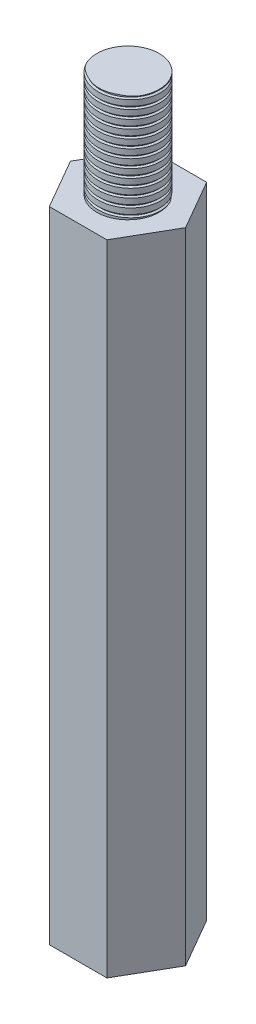
SolidWorks part; units mm, degrees
note: The reader was unsure of these and kept them because the rebuilt part matched: shared geometry of "草图1<3>".
ref_plane "前视基准面" through (0, 0, 0) normal (0, 0, 1) x (1, 0, 0)
ref_plane "上视基准面" through (0, 0, 0) normal (0, 1, 0) x (1, 0, 0)
ref_plane "右视基准面" through (0, 0, 0) normal (1, 0, 0) x (0, 0, -1)
sketch "草图1" plane through (0, 0, 0) normal (0, 1, 0) x (1, 0, 0)
  line L0 (0, 0) -> (0, 4.5761) construction
  line L1 (1.351, -2.34) -> (2.702, 0)
  line L2 (2.702, 0) -> (1.351, 2.34)
  line L3 (1.351, 2.34) -> (-1.351, 2.34)
  line L4 (-1.351, 2.34) -> (-2.702, 0)
  line L5 (-2.702, 0) -> (-1.351, -2.34)
  line L6 (-1.351, -2.34) -> (1.351, -2.34)
  line L7 (0, 4.5761) -> (0, -3.6794) construction
  circle A0 centre (0, 0) radius 2.34 construction
  circle A1 centre (0, 0) radius 1.46
  dimension "D1" = 4.68
  dimension "D2" = 2.92
extrude "凸台-拉伸1" add sketch "草图1" along normal blind 30 contours A1 | L5 L6 L1 L2 L3 L4 A1
extrude "切除-拉伸1" cut sketch "草图1<3>" along normal blind 5 contours A1
sketch "草图1<3>" plane through (0, 0, 0) normal (0, 1, 0) x (1, 0, 0) same geometry as "草图1"
sketch "草图2" plane through (0, 30, 0) normal (0, 1, 0) x (1, 0, 0)
  circle A0 centre (0, 0) radius 1.46
  dimension "D1" = 2.92
extrude "凸台-拉伸2" add sketch "草图2" along normal blind 5 separate body
ref_plane "基准面1" through (0, 0, 0) normal (0, 0, -1) x (-1, 0, 0)
sketch "草图4" plane through (0, 0, 0) normal (0, 0, -1) x (-1, 0, 0)
  line L0 (0, 0) -> (0, 28.5702) construction
  line L1 (-1.56, 30) -> (-1.56, 30.2)
  line L2 (-1.56, 30.2) -> (-1.36, 30.1333)
  line L3 (-1.36, 30.0667) -> (-1.56, 30)
  line L4 (-1.26, 30.1) -> (-2.0659, 30.1) construction
  line L5 (-2.0659, 30.1) -> (-0.8933, 30.1) construction
  line L7 (-1.46, 35) -> (-1.46, 30) construction
  line L8 (-1.36, 30.1333) -> (-1.36, 30.0667)
  line L9 (-1.46, 30) -> (1.46, 30) construction
  dimension "D1" = 0.1
  dimension "D2" = 0.1
  dimension "D3" = 0.1
  dimension "D4" = 0.3
  dimension "D5" = 0.2
  dimension "D6" = 0.1
  dimension "D7" = 0.0667
  dimension "D8" = 0.0667
ref_plane "基准面2" through (0, 30.1, 0) normal (0, 1, 0) x (1, 0, 0)
sketch "草图5" plane through (0, 30.1, 0) normal (0, 1, 0) x (1, 0, 0)
  circle A0 centre (0, 0) radius 1.46
  dimension "D1" = 2.92
curve "螺旋线/涡状线1" pitch 0.4 height 7.5 turns 18.75
sweep "切除-扫描1" cut profiles "草图4" path "螺旋线/涡状线1"
sketch "草图6" plane through (0, 0, 0) normal (0, -1, 0) x (1, 0, 0)
  circle A0 centre (0, 0) radius 1.46
curve "螺旋线/涡状线2" pitch 0.4 height 9.5 turns 23.75
sketch "草图7" plane through (0, 0, 0) normal (0, 0, -1) x (-1, 0, 0)
  line L0 (1.46, 0.2) -> (1.66, 0.1333)
  line L1 (1.66, 0.0667) -> (1.46, 0)
  line L2 (1.46, 0.2) -> (1.46, 0)
  line L3 (1.66, 0.1333) -> (1.66, 0.0667)
  line L8 (1.351, 0) -> (-1.351, 0) construction
  dimension "D1" = 0.2
  dimension "D3" = 1.46
  dimension "D4" = 0.2
sweep "切除-扫描2" cut profiles "草图7" path "螺旋线/涡状线2"
equation "\"chang\"= 20mm"
equation "\"r\"= 2.92mm"
equation "\"luowengao\"= 6.5mm"
equation "\"rr\"= 4.68mm"
equation "\"D1@草图1\"=\"rr\""
equation "\"D2@草图1\"=\"r\""
equation "\"D1@凸台-拉伸1\"=\"chang\""
equation "\"D1@切除-拉伸1\"=\"luowengao\"+5mm"
equation "\"D1@草图2\"=\"r\""
equation "\"D1@凸台-拉伸2\"=\"luowengao\""
